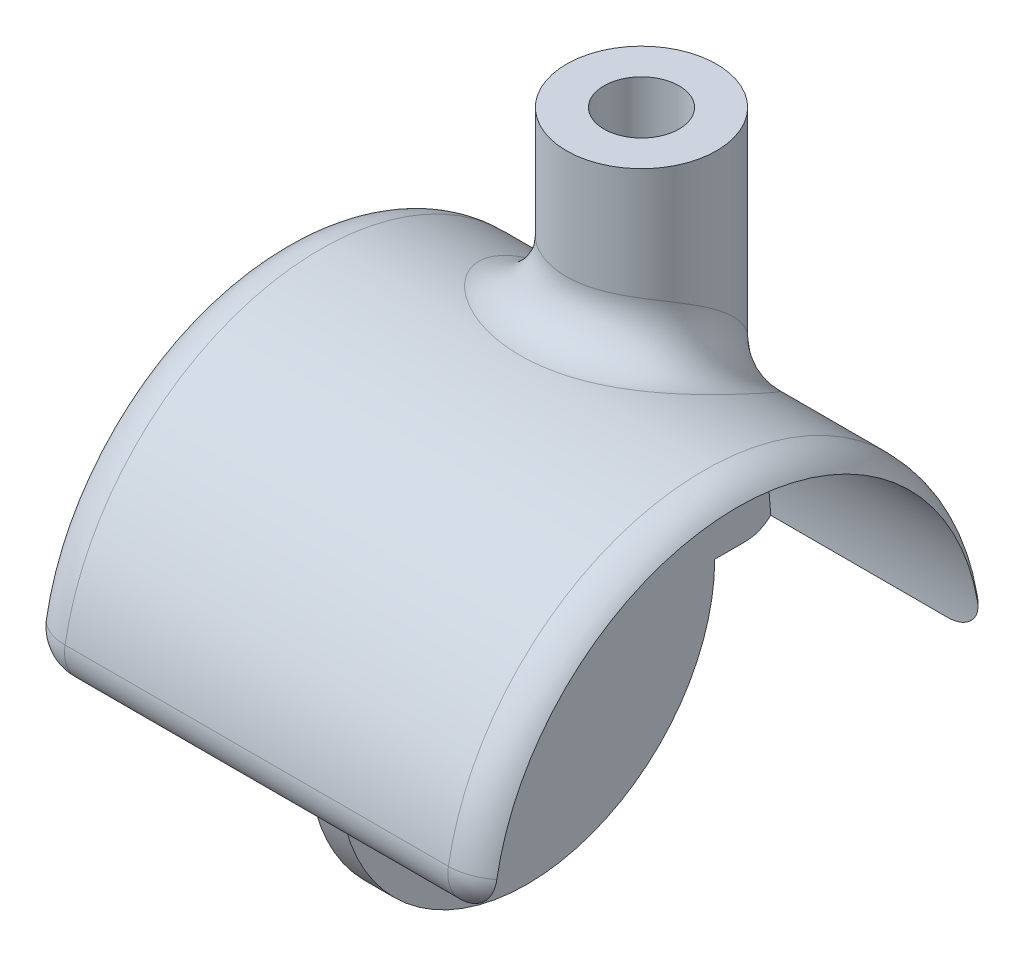
SolidWorks part; units mm, degrees
ref_plane "Front Plane" through (0, 0, 0) normal (0, 0, 1) x (1, 0, 0)
ref_plane "Top Plane" through (0, 0, 0) normal (0, 1, 0) x (1, 0, 0)
ref_plane "Right Plane" through (0, 0, 0) normal (1, 0, 0) x (0, 0, -1)
sketch "Sketch1" plane through (0, 0, 0) normal (1, 0, 0) x (0, 0, -1)
  line L0 (0, 0) -> (34.5, 0) construction
  line L1 (0, 0) -> (-34.5, 0) construction
  line L2 (0, 0) -> (0, 34.5) construction
  line L3 (-34.5, 0) -> (-32.5, 0)
  line L4 (34.5, 0) -> (32.5, 0)
  arc A0 (32.5, 0) -> (-32.5, 0) centre (0, 0) ccw
  arc A1 (34.5, 0) -> (-34.5, 0) centre (0, 0) ccw
  dimension "D1" = 65
  dimension "D2" = 2
  dimension "D3" = 90
  dimension "D4" = 90
extrude "Boss-Extrude1" add sketch "Sketch1" along normal mid plane 60
sketch "Sketch2" plane through (0, 0, 0) normal (1, 0, 0) x (0, 0, -1)
  line L0 (-32.5, 0) -> (-25, 0)
  line L1 (32.5, 0) -> (25, 0)
  arc A0 (-25, 0) -> (25, 0) centre (0, 0) ccw
  arc A1 (32.5, 0) -> (-32.5, 0) centre (0, 0) ccw
  circle A2 centre (0, 0) radius 5
  dimension "D1" = 50
  dimension "D2" = 10
extrude "Boss-Extrude2" add sketch "Sketch2" along normal mid plane 4
ref_plane "Plane1" through (0, 55, 0) normal (0, 1, 0) x (1, 0, 0)
sketch "Sketch3" plane through (0, 55, 0) normal (0, 1, 0) x (1, 0, 0)
  line L0 (0, 0) -> (0, 34.5) construction
  line L1 (30, 34.5) -> (-30, 34.5) construction
  circle A0 centre (0, 17.25) radius 10
  circle A1 centre (0, 17.25) radius 5
  dimension "D1" = 20
  dimension "D2" = 10
extrude "Boss-Extrude3" add sketch "Sketch3" against normal up to surface (21.2704 mm away) contours A0 | A1 up to face at (0, 17.25, 0)
fillet "Fillet1" radius 6 1 edges at (0.3259, 21.1655, -27.2447)
fillet "Fillet2" radius 6 2 edges at (-30, 34.5, 0) (30, 34.5, 0)
fillet "Fillet3" radius 5 2 edges at (0, 0, -34.5) (0, 0, 34.5) type face fillet first side face at (0, 0, 31.2443) first side face at (0, 0, -31.2443) second side face at (0.4261, 19.7046, -28.3192)
fillet "Fillet4" radius 5 1 edges at (0, 0, -34.5) type face fillet first side face at (0.4261, 19.7046, -28.3192) second side face at (0, 0, -31.2443)
